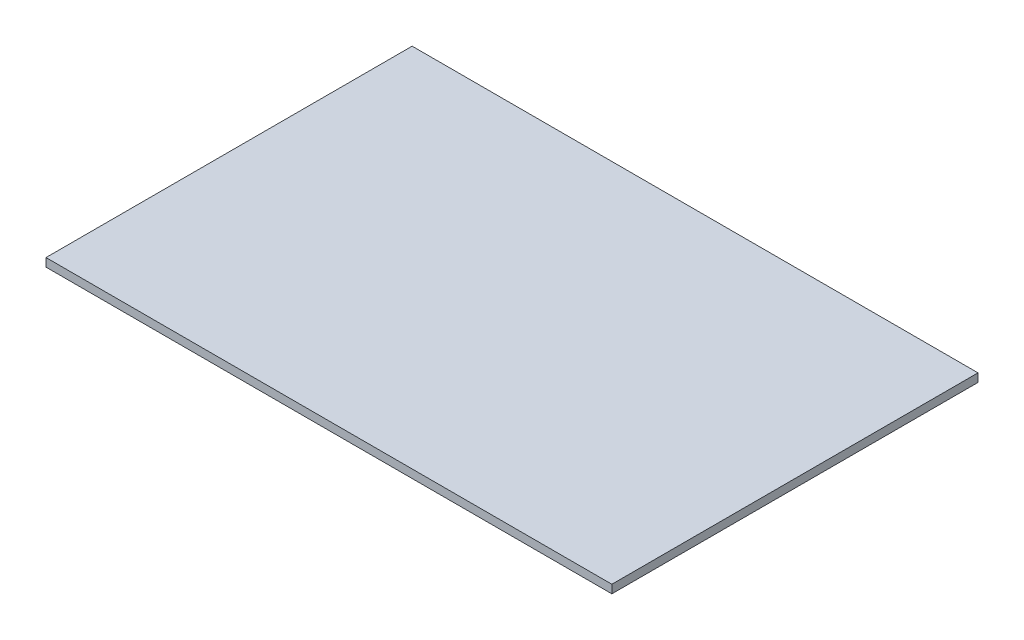
SolidWorks part; units mm, degrees
ref_plane "Front Plane" through (0, 0, 0) normal (0, 0, 1) x (1, 0, 0)
ref_plane "Top Plane" through (0, 0, 0) normal (0, 1, 0) x (1, 0, 0)
ref_plane "Right Plane" through (0, 0, 0) normal (1, 0, 0) x (0, 0, -1)
sketch "Sketch1" plane through (0, 0, 0) normal (0, 1, 0) x (1, 0, 0)
  line L1 (-170, 110) -> (170, 110)
  line L2 (-170, 110) -> (-170, -110)
  line L3 (-170, -110) -> (170, -110)
  line L4 (170, 110) -> (170, -110)
  line L5 (-170, 110) -> (170, -110) construction
  line L6 (-170, -110) -> (170, 110) construction
  point P0 (0, 0)
  dimension "D1" = 340
  dimension "D2" = 220
extrude "Boss-Extrude1" add sketch "Sketch1" along normal blind 5
